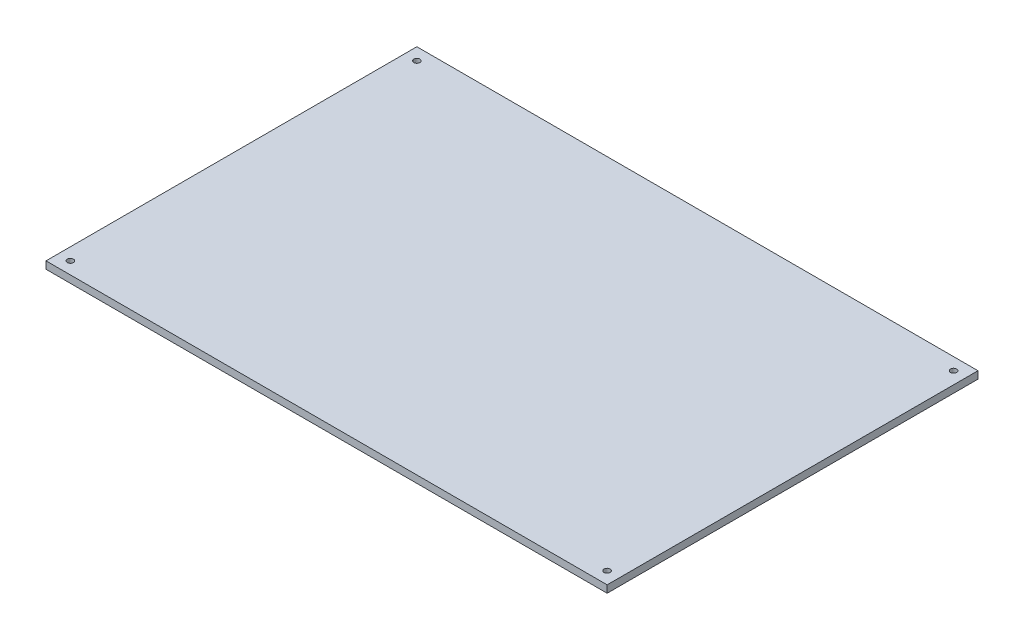
SolidWorks part; units mm, degrees
ref_plane "Спереди" through (0, 0, 0) normal (0, 0, 1) x (1, 0, 0)
ref_plane "Сверху" through (0, 0, 0) normal (0, 1, 0) x (1, 0, 0)
ref_plane "Справа" through (0, 0, 0) normal (1, 0, 0) x (0, 0, -1)
sketch "Эскиз1" plane through (0, 0, 0) normal (0, 1, 0) x (1, 0, 0)
  line L1 (-153.9032, 45.5) -> (76.0968, 45.5)
  line L2 (-153.9032, 45.5) -> (-153.9032, -106.5)
  line L3 (-153.9032, -106.5) -> (76.0968, -106.5)
  line L4 (76.0968, 45.5) -> (76.0968, -106.5)
  dimension "D1" = 230
  dimension "D2" = 152
extrude "Бобышка-Вытянуть1" add sketch "Эскиз1" along normal blind 3
sketch "Эскиз2" plane through (0, 3, 0) normal (0, 1, 0) x (1, 0, 0)
  line L0 (76.0968, 45.5) -> (-153.9032, 45.5) construction
  line L1 (-153.9032, 45.5) -> (-153.9032, -106.5) construction
  line L2 (76.0968, -106.5) -> (76.0968, 45.5) construction
  line L3 (-153.9032, -106.5) -> (76.0968, -106.5) construction
  circle A0 centre (-148.9032, 40.5) radius 1.25
  circle A1 centre (71.0968, 40.5) radius 1.25
  circle A2 centre (71.0968, -101.5) radius 1.25
  circle A3 centre (-148.9032, -101.5) radius 1.25
  dimension "D1" = 2.5
  dimension "D2" = 2.5
  dimension "D3" = 2.5
  dimension "D4" = 2.5
  dimension "D5" = 5
  dimension "D6" = 5
  dimension "D7" = 5
  dimension "D8" = 5
  dimension "D9" = 5
  dimension "D10" = 5
  dimension "D11" = 5
  dimension "D12" = 5
extrude "Вырез-Вытянуть1" cut sketch "Эскиз2" against normal blind 3
